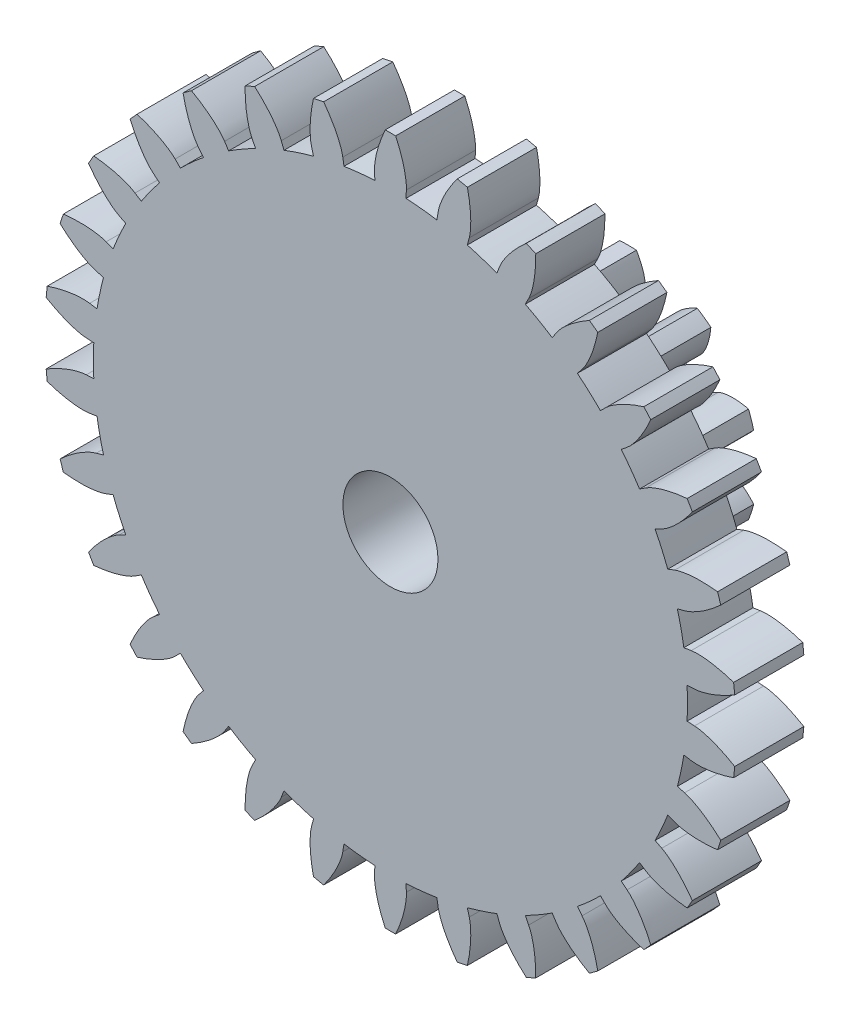
SolidWorks part; units mm, degrees
ref_plane "前视基准面" through (0, 0, 0) normal (0, 0, 1) x (1, 0, 0)
ref_plane "上视基准面" through (0, 0, 0) normal (0, 1, 0) x (1, 0, 0)
ref_plane "右视基准面" through (0, 0, 0) normal (1, 0, 0) x (0, 0, -1)
other "Configuration Table"
sketch "草图1" plane through (0, 0, 0) normal (0, 0, 1) x (1, 0, 0)
  line L0 (0, 0) -> (2.5, 0) construction
  line L1 (0, 0) -> (2.4692, 0.3911) construction
  line L2 (0, 0) -> (2.324, 0.3431)
  line L3 (2.4692, 0.3911) -> (2.4692, -0.3911) construction
  line L4 (0, 0) -> (2.324, -0.3431)
  circle A0 centre (0, 0) radius 3
  circle A1 centre (0, 0) radius 2.5 construction
  circle A2 centre (0, 0) radius 1.875
  circle A3 centre (0, 0) radius 2.3492 construction
  circle A4 centre (0, 0) radius 1.1
  spline S0 degree 4 poles (2.324, 0.3431) (2.3418, 0.3457) (2.3907, 0.3567) (2.48, 0.3921) (2.6156, 0.4687) (2.774, 0.5944) (2.9524, 0.7829) (3.1261, 1.0328) (3.2755, 1.3318) (3.3905, 1.6731) (3.4623, 2.0258) (3.4939, 2.3843) (3.4875, 2.7617) (3.431, 3.2258) (3.293, 3.7669) (3.0427, 4.3657) (2.6648, 4.9798) (2.2034, 5.533) (1.6708, 6.0186) (1.0824, 6.4323) (0.4456, 6.7712) (-0.2216, 7.0345) (-0.9214, 7.2211) (-1.5352, 7.3195) (-2.0864, 7.356) (-2.4818, 7.3587) (-2.8333, 7.3427) (-3.0656, 7.3237) (-3.3922, 7.2873) (-3.6372, 7.2455) (-3.8821, 7.2011) (-4.0043, 7.1711) (-4.0832, 7.1539) knots 0 0 0 0 0 0.005604 0.015718 0.02996 0.048734 0.068727 0.096889 0.125051 0.153212 0.181374 0.209535 0.237696 0.271429 0.327752 0.384075 0.440398 0.496721 0.553044 0.609367 0.66569 0.722013 0.778336 0.834659 0.86282 0.890982 0.909091 0.931818 0.954545 0.977273 1 1 1 1 1 construction
  spline S1 degree 4 poles (2.324, 0.3431) (2.3418, 0.3457) (2.3907, 0.3567) (2.48, 0.3921) (2.6156, 0.4687) (2.774, 0.5944) (2.9524, 0.7829) (3.1261, 1.0328) (3.2755, 1.3318) (3.3905, 1.6731) (3.4623, 2.0258) (3.4939, 2.3843) (3.4875, 2.7617) (3.431, 3.2258) (3.293, 3.7669) (3.0427, 4.3657) (2.6648, 4.9798) (2.2034, 5.533) (1.6708, 6.0186) (1.0824, 6.4323) (0.4456, 6.7712) (-0.2216, 7.0345) (-0.9214, 7.2211) (-1.5352, 7.3195) (-2.0864, 7.356) (-2.4818, 7.3587) (-2.7511, 7.3465) (-2.8848, 7.3375) (-2.9371, 7.3334) knots 0 0 0 0 0 0.005604 0.015718 0.02996 0.048734 0.068727 0.096889 0.125051 0.153212 0.181374 0.209535 0.237696 0.271429 0.327752 0.384075 0.440398 0.496721 0.553044 0.609367 0.66569 0.722013 0.778336 0.834659 0.86282 0.890982 0.909091 0.909091 0.909091 0.909091 0.909091
  spline S2 degree 4 poles (2.324, -0.3431) (2.3418, -0.3457) (2.3907, -0.3567) (2.48, -0.3921) (2.6156, -0.4687) (2.774, -0.5944) (2.9524, -0.7829) (3.1261, -1.0328) (3.2755, -1.3318) (3.3905, -1.6731) (3.4623, -2.0258) (3.4939, -2.3843) (3.4875, -2.7617) (3.431, -3.2258) (3.293, -3.7669) (3.0427, -4.3657) (2.6648, -4.9798) (2.2034, -5.533) (1.6708, -6.0186) (1.0824, -6.4323) (0.4456, -6.7712) (-0.2216, -7.0345) (-0.9214, -7.2211) (-1.5352, -7.3195) (-2.0864, -7.356) (-2.4818, -7.3587) (-2.8333, -7.3427) (-3.0656, -7.3237) (-3.3922, -7.2873) (-3.6372, -7.2455) (-3.8821, -7.2011) (-4.0043, -7.1711) (-4.0832, -7.1539) knots 0 0 0 0 0 0.005604 0.015718 0.02996 0.048734 0.068727 0.096889 0.125051 0.153212 0.181374 0.209535 0.237696 0.271429 0.327752 0.384075 0.440398 0.496721 0.553044 0.609367 0.66569 0.722013 0.778336 0.834659 0.86282 0.890982 0.909091 0.931818 0.954545 0.977273 1 1 1 1 1 construction
  spline S3 degree 4 poles (2.324, -0.3431) (2.3418, -0.3457) (2.3907, -0.3567) (2.48, -0.3921) (2.6156, -0.4687) (2.774, -0.5944) (2.9524, -0.7829) (3.1261, -1.0328) (3.2755, -1.3318) (3.3905, -1.6731) (3.4623, -2.0258) (3.4939, -2.3843) (3.4875, -2.7617) (3.431, -3.2258) (3.293, -3.7669) (3.0427, -4.3657) (2.6648, -4.9798) (2.2034, -5.533) (1.6708, -6.0186) (1.0824, -6.4323) (0.4456, -6.7712) (-0.2216, -7.0345) (-0.9214, -7.2211) (-1.5352, -7.3195) (-2.0864, -7.356) (-2.4818, -7.3587) (-2.7511, -7.3465) (-2.8848, -7.3375) (-2.9371, -7.3334) knots 0 0 0 0 0 0.005604 0.015718 0.02996 0.048734 0.068727 0.096889 0.125051 0.153212 0.181374 0.209535 0.237696 0.271429 0.327752 0.384075 0.440398 0.496721 0.553044 0.609367 0.66569 0.722013 0.778336 0.834659 0.86282 0.890982 0.909091 0.909091 0.909091 0.909091 0.909091
  point P15 (2.4692, 0)
  dimension "齿顶圆直径" = 6
  dimension "分度圆直径" = 5
  dimension "齿根圆直径" = 3.75
  dimension "基圆直径" = 4.6985
  dimension "内孔直径" = 2.2
  dimension "渐近线镜像线夹角" = 9
extrude "凸台-拉伸1" add sketch "草图1" along normal blind 3.9 contours A0 | A4
extrude "切除-拉伸1" cut sketch "草图1<3>" along normal through all contours A2 S3 A0 S1 region at (2.52, 0, 0)
sketch "草图1<3>" plane through (0, 0, 0) normal (0, 0, 1) x (1, 0, 0) same geometry as "草图1"
pattern_circular "阵列(圆周)1" count 10 every 36 about axis through (0, 0, 3.9) along (0, 0, 1) of "切除-拉伸1"
sketch "草图2" plane through (0, 0, 3.9) normal (0, 0, 1) x (1, 0, 0)
  line L0 (0, 0) -> (7.5, 0) construction
  line L1 (0, 0) -> (7.038, 0.3688)
  line L2 (0, 0) -> (7.038, -0.3688)
  line L3 (7.038, 0.3688) -> (7.038, -0.3688) construction
  circle A0 centre (0, 0) radius 7.5 construction
  circle A1 centre (0, 0) radius 7.0477 construction
  circle A2 centre (0, 0) radius 6.875
  circle A3 centre (0, 0) radius 8
  circle A4 centre (0, 0) radius 1.1
  spline S0 degree 4 poles (7.038, -0.3688) (7.0648, -0.3703) (7.1181, -0.3756) (7.2661, -0.4036) (7.54, -0.4903) (7.9387, -0.6789) (8.4412, -1.0177) (9.0178, -1.5414) (9.5944, -2.2492) (10.1095, -3.1096) (10.5312, -4.1044) (10.8266, -5.1431) (11.0027, -6.2081) (11.0697, -7.3387) (11.0063, -8.7398) (10.7169, -10.3898) (10.1042, -12.238) (9.1146, -14.161) (7.8594, -15.921) (6.3787, -17.4949) (4.7097, -18.8667) (3.115, -19.8807) (1.6719, -20.6128) (0.4283, -21.1308) (-0.5886, -21.4897) (-1.622, -21.7931) (-2.6724, -22.0413) (-3.73, -22.2344) (-4.6701, -22.3557) (-5.4675, -22.426) (-6.1046, -22.4596) (-6.5222, -22.4739) (-6.9919, -22.4794) (-7.2978, -22.4782) (-7.7905, -22.469) (-8.174, -22.4512) (-8.6389, -22.4248) (-9.053, -22.3901) (-9.4984, -22.3472) (-9.9204, -22.296) (-10.2509, -22.2515) (-10.4614, -22.2192) (-10.5706, -22.2024) knots 0 0 0 0 0 0.002802 0.005604 0.015718 0.02996 0.048734 0.068727 0.096889 0.125051 0.153212 0.181374 0.209535 0.237696 0.271429 0.327752 0.384075 0.440398 0.496721 0.553044 0.609367 0.66569 0.693852 0.722013 0.750174 0.778336 0.806497 0.834659 0.86282 0.876901 0.890982 0.900036 0.909091 0.920455 0.931818 0.943182 0.954545 0.965909 0.977273 0.988636 1 1 1 1 1 construction
  spline S1 degree 4 poles (7.038, -0.3688) (7.0648, -0.3703) (7.1181, -0.3756) (7.2661, -0.4036) (7.54, -0.4903) (7.9387, -0.6789) (8.4412, -1.0177) (9.0178, -1.5414) (9.5944, -2.2492) (10.1095, -3.1096) (10.5312, -4.1044) (10.8266, -5.1431) (11.0027, -6.2081) (11.0697, -7.3387) (11.0063, -8.7398) (10.7169, -10.3898) (10.1042, -12.238) (9.1146, -14.161) (7.8594, -15.921) (6.3787, -17.4949) (4.7097, -18.8667) (3.115, -19.8807) (1.6719, -20.6128) (0.4283, -21.1308) (-0.5886, -21.4897) (-1.622, -21.7931) (-2.6724, -22.0413) (-3.73, -22.2344) (-4.6701, -22.3557) (-5.4675, -22.426) (-6.1046, -22.4596) (-6.5222, -22.4739) (-6.8693, -22.478) (-7.028, -22.4785) (-7.1067, -22.4783) knots 0 0 0 0 0 0.002802 0.005604 0.015718 0.02996 0.048734 0.068727 0.096889 0.125051 0.153212 0.181374 0.209535 0.237696 0.271429 0.327752 0.384075 0.440398 0.496721 0.553044 0.609367 0.66569 0.693852 0.722013 0.750174 0.778336 0.806497 0.834659 0.86282 0.876901 0.890982 0.900036 0.909091 0.909091 0.909091 0.909091 0.909091
  spline S2 degree 4 poles (7.038, 0.3688) (7.0648, 0.3703) (7.1181, 0.3756) (7.2661, 0.4036) (7.54, 0.4903) (7.9387, 0.6789) (8.4412, 1.0177) (9.0178, 1.5414) (9.5944, 2.2492) (10.1095, 3.1096) (10.5312, 4.1044) (10.8266, 5.1431) (11.0027, 6.2081) (11.0697, 7.3387) (11.0063, 8.7398) (10.7169, 10.3898) (10.1042, 12.238) (9.1146, 14.161) (7.8594, 15.921) (6.3787, 17.4949) (4.7097, 18.8667) (3.115, 19.8807) (1.6719, 20.6128) (0.4283, 21.1308) (-0.5886, 21.4897) (-1.622, 21.7931) (-2.6724, 22.0413) (-3.73, 22.2344) (-4.6701, 22.3557) (-5.4675, 22.426) (-6.1046, 22.4596) (-6.5222, 22.4739) (-6.9919, 22.4794) (-7.2978, 22.4782) (-7.7905, 22.469) (-8.174, 22.4512) (-8.6389, 22.4248) (-9.053, 22.3901) (-9.4984, 22.3472) (-9.9204, 22.296) (-10.2509, 22.2515) (-10.4614, 22.2192) (-10.5706, 22.2024) knots 0 0 0 0 0 0.002802 0.005604 0.015718 0.02996 0.048734 0.068727 0.096889 0.125051 0.153212 0.181374 0.209535 0.237696 0.271429 0.327752 0.384075 0.440398 0.496721 0.553044 0.609367 0.66569 0.693852 0.722013 0.750174 0.778336 0.806497 0.834659 0.86282 0.876901 0.890982 0.900036 0.909091 0.920455 0.931818 0.943182 0.954545 0.965909 0.977273 0.988636 1 1 1 1 1 construction
  spline S3 degree 4 poles (7.038, 0.3688) (7.0648, 0.3703) (7.1181, 0.3756) (7.2661, 0.4036) (7.54, 0.4903) (7.9387, 0.6789) (8.4412, 1.0177) (9.0178, 1.5414) (9.5944, 2.2492) (10.1095, 3.1096) (10.5312, 4.1044) (10.8266, 5.1431) (11.0027, 6.2081) (11.0697, 7.3387) (11.0063, 8.7398) (10.7169, 10.3898) (10.1042, 12.238) (9.1146, 14.161) (7.8594, 15.921) (6.3787, 17.4949) (4.7097, 18.8667) (3.115, 19.8807) (1.6719, 20.6128) (0.4283, 21.1308) (-0.5886, 21.4897) (-1.622, 21.7931) (-2.6724, 22.0413) (-3.73, 22.2344) (-4.6701, 22.3557) (-5.4675, 22.426) (-6.1046, 22.4596) (-6.5222, 22.4739) (-6.8693, 22.478) (-7.028, 22.4785) (-7.1067, 22.4783) knots 0 0 0 0 0 0.002802 0.005604 0.015718 0.02996 0.048734 0.068727 0.096889 0.125051 0.153212 0.181374 0.209535 0.237696 0.271429 0.327752 0.384075 0.440398 0.496721 0.553044 0.609367 0.66569 0.693852 0.722013 0.750174 0.778336 0.806497 0.834659 0.86282 0.876901 0.890982 0.900036 0.909091 0.909091 0.909091 0.909091 0.909091
  point P16 (7.038, 0)
  dimension "内孔直径" = 2.2
  dimension "分度圆直径" = 15
  dimension "齿顶圆直径" = 16
  dimension "基圆直径" = 14.0954
  dimension "齿根圆直径" = 13.75
  dimension "渐开线镜像线夹角" = 3
extrude "凸台-拉伸2" add sketch "草图2" along normal blind 1.6 contours A3 | A4
extrude "切除-拉伸3" cut sketch "草图2<3>" along normal through all contours S3 L1 A2 L2 S1 A3 region at (7.5024, 0, 3.9)
sketch "草图2<3>" plane through (0, 0, 3.9) normal (0, 0, 1) x (1, 0, 0) same geometry as "草图2"
pattern_circular "阵列(圆周)2" count 30 over 360 about axis through (0, 0, 5.5) along (0, 0, 1) of "切除-拉伸3"
equation "\"m\" = 0.5'模数"
equation "\"z\" = 10'齿数"
equation "\"a\"= 20度'压力角"
equation "\"d\"= \"m\" * \"z\"'分度圆直径"
equation "\"da\"= ( \"z\" + 2 ) * \"m\"'齿顶圆直径"
equation "\"df\"= ( \"z\" - 2.5 ) * \"m\"'齿根圆直径"
equation "\"s\"= 0.5 * PI * \"m\"'分度圆齿厚"
equation "\"r\"= 0.38 * \"m\"'齿根圆角"
equation "\"B\"= 0.3 * \"d\"'齿厚"
equation "\"db\"= \"m\" * \"z\" * cos ( \"a\" )'基圆直径"
equation "\"rb\"= \"db\" / 2'基圆半径"
equation "\"齿顶圆直径@草图1\"= \"da\""
equation "\"分度圆直径@草图1\"= \"d\""
equation "\"齿根圆直径@草图1\"= \"df\""
equation "\"基圆直径@草图1\"= \"db\""
equation "\"渐近线镜像线夹角@草图1\"= 360 / 4 / \"z\""
equation "\"h\" = 3.9mm'齿轮厚度"
equation "\"ir\"= 2.2mm'内孔直径"
equation "\"内孔直径@草图1\"= \"ir\""
equation "\"齿轮厚@凸台-拉伸1\"= \"h\""
equation "\"齿轮夹角@阵列(圆周)1\"= 360 / \"z\""
equation "\"齿数@阵列(圆周)1\"= \"z\""
equation "\"m1\" = 0.5'模数"
equation "\"z1\"= 30'齿数"
equation "\"a1\"= 20度'压力角"
equation "\"d1\"= \"m1\" * \"z1\"'分度圆直径"
equation "\"da1\"= ( \"z1\" + 2 ) * \"m1\"'齿顶圆直径"
equation "\"df1\"= ( \"z1\" - 2.5 ) * \"m1\"'齿根圆直径"
equation "\"s1\"= 0.5 * PI * \"m1\"'分度圆齿厚"
equation "\"r1\"= 0.38 * \"m1\"'齿根圆角"
equation "\"B1\"= 0.3 * \"d1\"'齿厚"
equation "\"db1\"= \"m1\" * \"z1\" * cos ( \"a1\" )'基圆直径"
equation "\"rb1\"= \"db1\" / 2'基圆半径"
equation "\"分度圆直径@草图2\"= \"d1\""
equation "\"齿顶圆直径@草图2\"= \"da1\""
equation "\"基圆直径@草图2\"= \"db1\""
equation "\"齿根圆直径@草图2\"= \"df1\""
equation "\"渐开线镜像线夹角@草图2\"= 360 / 4 / \"z1\""
equation "\"内孔直径@草图2\"= \"ir\""
equation "\"二层齿轮厚@凸台-拉伸2\" = \"h1\""
equation "\"h1\" = 1.6'齿轮厚度"
equation "\"二层齿数@阵列(圆周)2\"= \"z1\""
